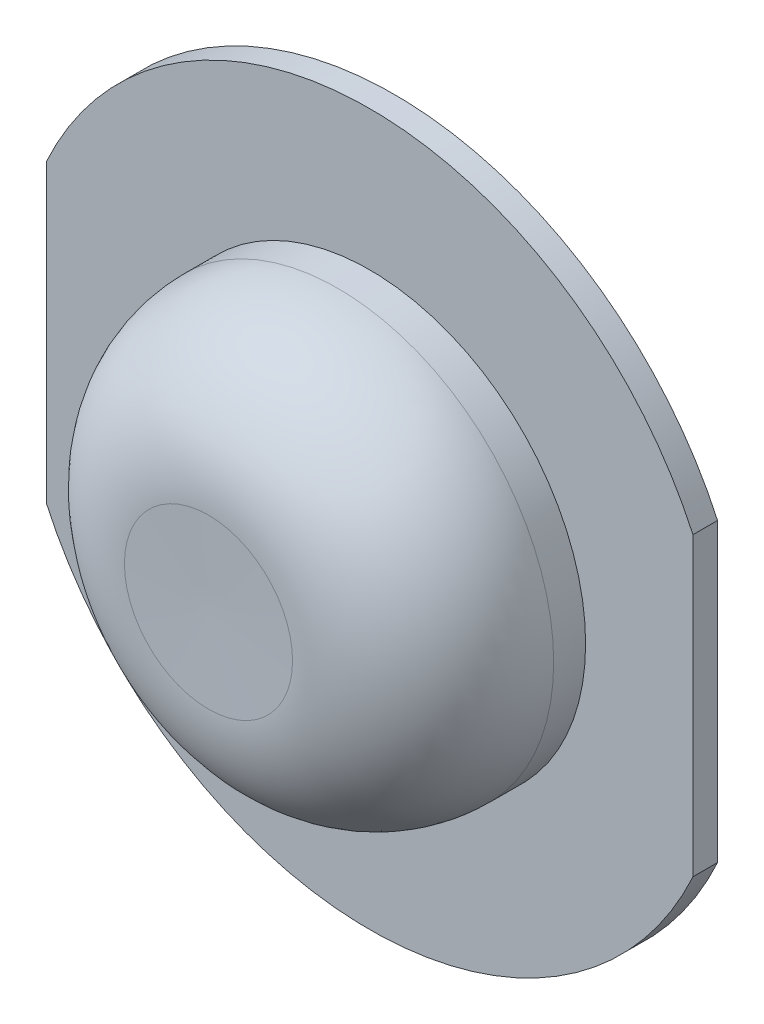
SolidWorks part; units mm, degrees
material "Silicon"
ref_plane "Front Plane" through (0, 0, 0) normal (0, 0, 1) x (1, 0, 0)
ref_plane "Top Plane" through (0, 0, 0) normal (0, 1, 0) x (1, 0, 0)
ref_plane "Right Plane" through (0, 0, 0) normal (1, 0, 0) x (0, 0, -1)
sketch "Sketch1" plane through (0, 0, 0) normal (0, 0, 1) x (1, 0, 0)
  line L0 (50, 22.9129) -> (50, -22.9129)
  line L1 (-50, 22.9129) -> (-50, -22.9129)
  arc A0 (-50, -22.9129) -> (50, -22.9129) centre (0, 0) ccw
  arc A1 (50, 22.9129) -> (-50, 22.9129) centre (0, 0) ccw
  dimension "D1" = 55
  dimension "D2" = 100
extrude "Boss-Extrude1" add sketch "Sketch1" along normal blind 3.8
sketch "Sketch3" plane through (0, 0, 0) normal (0, 1, 0) x (1, 0, 0)
  line L0 (0, -3.8) -> (0, -28.48)
  line L1 (0, -3.8) -> (33.395, -3.8)
  line L2 (33.395, -3.8) -> (33.395, -8.7407)
  line L3 (0, -28.48) -> (13, -28.7368)
  line L4 (-50, -3.8) -> (50, -3.8) construction
  arc A0 (33.395, -8.7407) -> (13, -28.7368) centre (13.395, -8.7407) cw
  dimension "D3" = 20
  dimension "D1" = 33.395
  dimension "D2" = 24.68
  dimension "D4" = 13
revolve "Revolve1" add sketch "Sketch3" angle 360 about L0
sketch "Sketch4" plane through (0, 0, 0) normal (0, 0, -1) x (-1, 0, 0)
  line L1 (21.65, 21.65) -> (-21.65, 21.65)
  line L2 (21.65, 21.65) -> (21.65, -21.65)
  line L3 (21.65, -21.65) -> (-21.65, -21.65)
  line L4 (-21.65, 21.65) -> (-21.65, -21.65)
  line L5 (21.65, 21.65) -> (-21.65, -21.65) construction
  line L6 (21.65, -21.65) -> (-21.65, 21.65) construction
  point P0 (0, 0)
  dimension "D1" = 43.3
extrude "Cut-Extrude1" cut sketch "Sketch4" against normal blind 3
